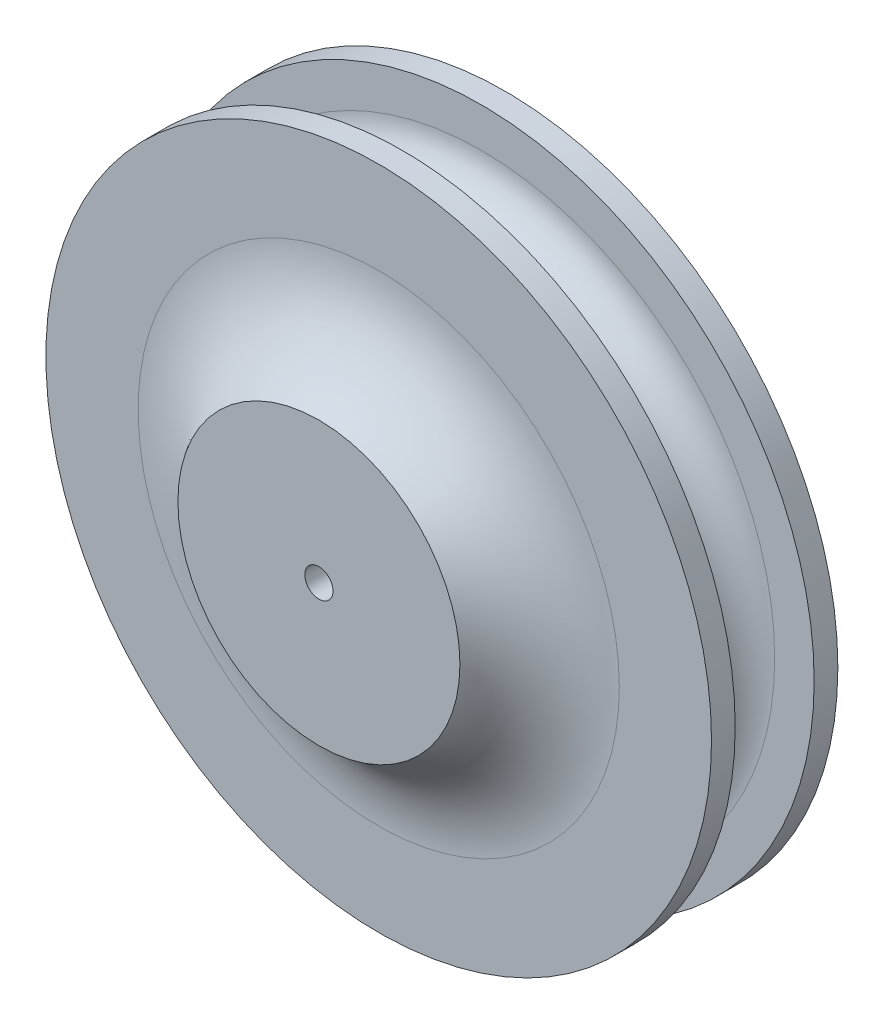
SolidWorks part; units mm, degrees
material "ALUMINUM 6061-T6; 6061-T651"
ref_plane "Front Plane" through (0, 0, 0) normal (0, 0, 1) x (1, 0, 0)
ref_plane "Top Plane" through (0, 0, 0) normal (0, 1, 0) x (1, 0, 0)
ref_plane "Right Plane" through (0, 0, 0) normal (1, 0, 0) x (0, 0, -1)
sketch "Sketch1" plane through (0, 0, 0) normal (0, 0, 1) x (1, 0, 0)
  line L0 (0, 16.51) -> (0, 0) construction
  line L1 (0, 0) -> (0, -16.51) construction
  circle A0 centre (0, 0) radius 14.2875 construction
  circle A1 centre (0, 16.51) radius 2.2225 construction
  circle A2 centre (0, -16.51) radius 2.2225 construction
  dimension "D1" = 28.575
  dimension "D2" = 4.445
sketch "Sketch2" plane through (0, 0, 0) normal (0, 0, 1) x (1, 0, 0)
  circle A0 centre (0, 0) radius 18.7325
  circle A1 centre (0, 16.51) radius 2.2225 construction
extrude "Boss-Extrude1" add sketch "Sketch2" along normal blind 3.556 and the other way blind 3.556
sketch "Sketch3" plane through (0, 0, 0) normal (1, 0, 0) x (0, 0, -1)
  line L0 (0, 18.7325) -> (0, 14.2875) construction
  line L1 (0, 18.7325) -> (0, 14.2875) construction
  line L2 (-3.556, 0) -> (3.556, 0) construction
  line L3 (-3.556, 18.7325) -> (-3.556, -18.7325) construction
  line L4 (3.556, -18.7325) -> (3.556, 18.7325) construction
  line L5 (-2.2225, 16.51) -> (-2.2225, 20.955)
  line L6 (2.2225, 16.51) -> (2.2225, 20.955)
  line L7 (2.2225, 20.955) -> (-2.2225, 20.955)
  line L8 (3.556, 18.7325) -> (-3.556, 18.7325) construction
  arc A0 (-2.2225, 16.51) -> (2.2225, 16.51) centre (0, 16.51) ccw
  point P16 (2.2225, 18.7325)
revolve "Cut-Revolve1" cut sketch "Sketch3" angle 360 about L2
sketch "Sketch4" plane through (0, 0, 0) normal (0, 0, 1) x (1, 0, 0)
  circle A0 centre (0, 0) radius 7.9375
  dimension "D1" = 15.875
extrude "Boss-Extrude2" add sketch "Sketch4" along normal blind 6.9215 and the other way blind 6.9215
fillet "Fillet1" radius 6.35 2 edges at (7.9375, 0, 3.556) (7.9375, 0, -3.556)
sketch "Sketch5" plane through (0, 0, 6.9215) normal (0, 0, 1) x (1, 0, 0)
  circle A0 centre (0, 0) radius 0.7937
  dimension "D1" = 1.5875
extrude "Cut-Extrude1" cut sketch "Sketch5" against normal through all both and the other way through all
